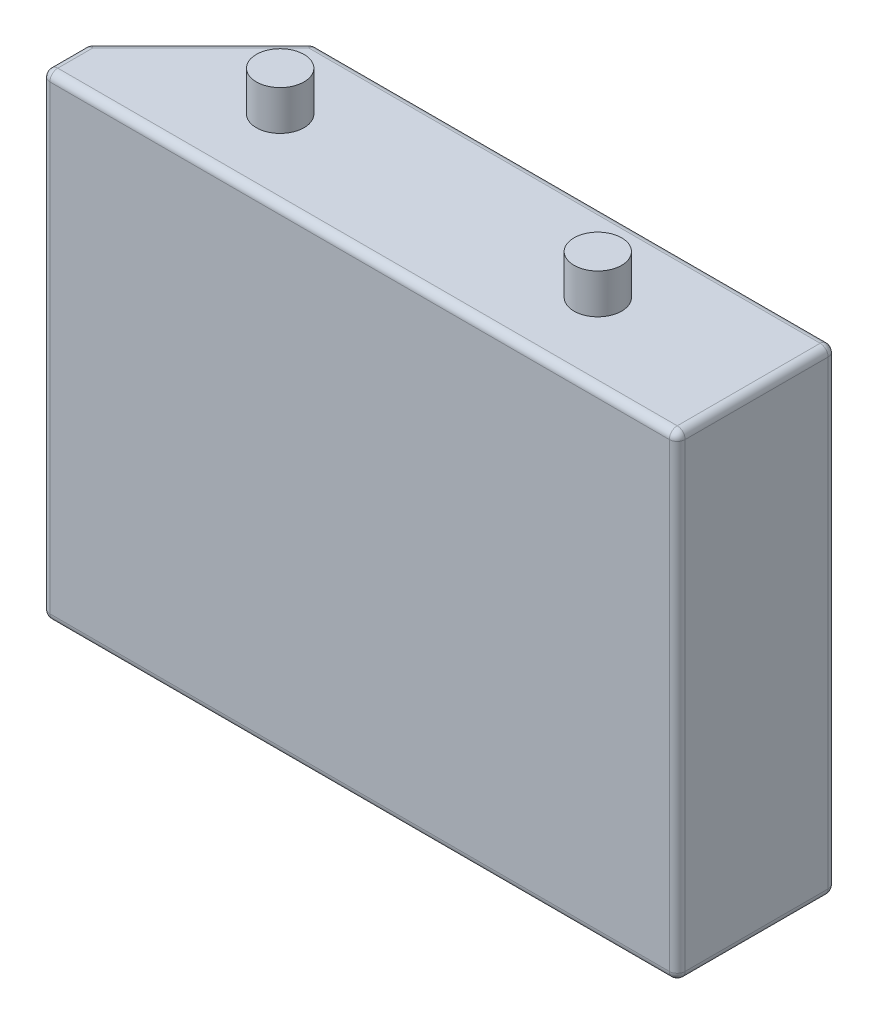
SolidWorks part; units mm, degrees
ref_plane "Front Plane" through (0, 0, 0) normal (0, 0, 1) x (1, 0, 0)
ref_plane "Top Plane" through (0, 0, 0) normal (0, 1, 0) x (1, 0, 0)
ref_plane "Right Plane" through (0, 0, 0) normal (1, 0, 0) x (0, 0, -1)
sketch "Sketch1" plane through (0, 0, 0) normal (0, 0, 1) x (1, 0, 0)
  line L1 (400, -300) -> (-400, -300)
  line L2 (400, -300) -> (400, 300)
  line L3 (400, 300) -> (-400, 300)
  line L4 (-400, -300) -> (-400, 300)
  line L5 (400, -300) -> (-400, 300) construction
  line L6 (400, 300) -> (-400, -300) construction
  point P0 (0, 0)
  dimension "D1" = 800
  dimension "D2" = 600
extrude "Boss-Extrude1" add sketch "Sketch1" along normal blind 200
sketch "Sketch2" plane through (0, 300, 0) normal (0, 1, 0) x (1, 0, 0)
  line L0 (0, 0) -> (0, -200) construction
  line L1 (400, -200) -> (-400, -200) construction
  line L2 (-400, -100) -> (400, -100) construction
  line L3 (-400, -200) -> (-400, 0) construction
  line L4 (400, -200) -> (400, 0) construction
  circle A0 centre (200, -100) radius 30
  circle A1 centre (-200, -100) radius 30
  dimension "D1" = 60
  dimension "D2" = 200
extrude "Boss-Extrude2" add sketch "Sketch2" along normal blind 50
mirror "Mirror1" about plane through (0, 0, 0) normal (0, 1, 0) of "Boss-Extrude2"
fillet "Fillet1" radius 10 12 edges at (400, -300, 100) (400, 0, 200) (400, 300, 100) (400, 0, 0) (0, -300, 200) (0, 300, 200) (0, -300, 0) (-400, -300, 100) (-400, 0, 200) (-400, 300, 100) (-400, 0, 0) (0, 300, 0)
sketch "Sketch4" plane through (0, 300, 0) normal (0, 1, 0) x (1, 0, 0)
  line L0 (-257.9661, 0) -> (-400, -142.0339)
  line L1 (-400, -142.0339) -> (-400, 0)
  line L2 (-400, 0) -> (-257.9661, 0)
  line L3 (-390, 0) -> (390, 0) construction
  line L4 (-400, -190) -> (-400, -10) construction
  point P7 (-350, -92.0339)
  dimension "D1" = 45
extrude "Cut-Extrude3" cut sketch "Sketch4" against normal through all contours L2 L0 L1
fillet "Fillet2" radius 10 8 edges at (-260.895, -297.0711, 2.9289) (-257.9661, 0, 0) (-260.895, 297.0711, 2.9289) (-328.983, 300, 71.017) (-397.0711, 297.0711, 139.105) (-400, 0, 142.0339) (-397.0711, -297.0711, 139.105) (-328.983, -300, 71.017)
sketch "Sketch5" plane through (-128.983, 0, -128.983) normal (-0.7071, 0, -0.7071) x (-0.7071, 0, 0.7071)
  text T0 "R.PX0" font "@Adobe Gothic Std B" height 80
extrude "Cut-Extrude4" cut sketch "Sketch5" against normal blind 5
